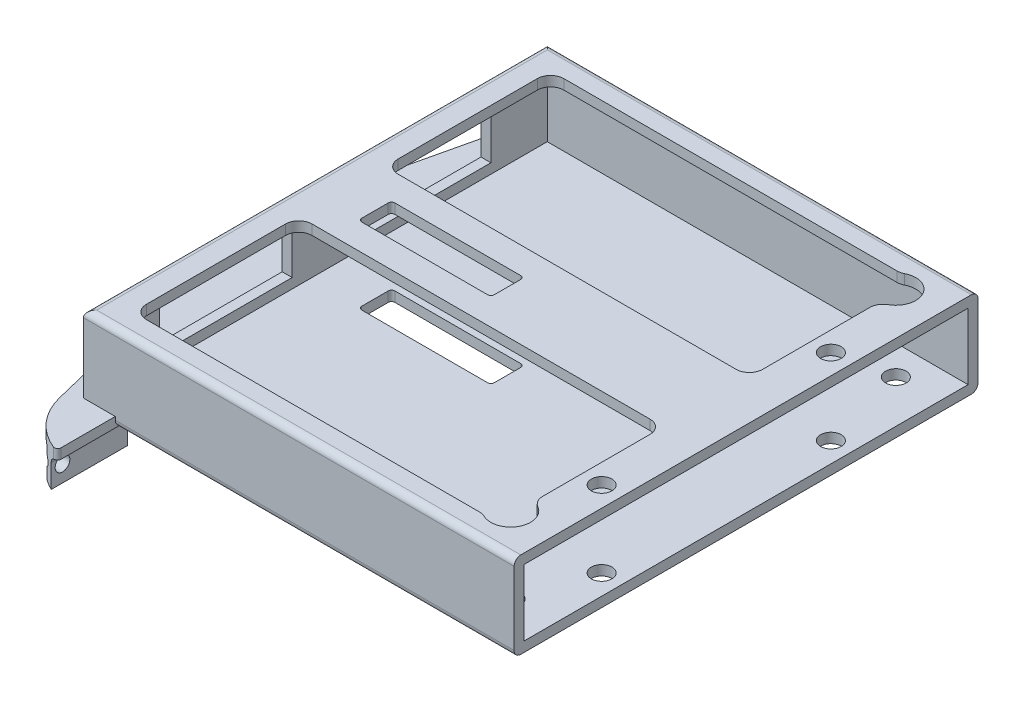
SolidWorks part; units mm, degrees
ref_plane "Front Plane" through (0, 0, 0) normal (0, 0, 1) x (1, 0, 0)
ref_plane "Top Plane" through (0, 0, 0) normal (0, 1, 0) x (1, 0, 0)
ref_plane "Right Plane" through (0, 0, 0) normal (1, 0, 0) x (0, 0, -1)
sketch "Sketch1" plane through (0, 0, 0) normal (0, 1, 0) x (1, 0, 0)
  line L0 (-33.0169, 20.6113) -> (31.9831, 20.6113)
  line L1 (-33.0169, 20.6113) -> (-33.0169, -49.3887)
  line L2 (31.9831, 20.6113) -> (31.9831, -49.3887)
  line L3 (-33.0169, -49.3887) -> (31.9831, -49.3887)
  dimension "D1" = 65
  dimension "D2" = 70
extrude "Boss-Extrude1" add sketch "Sketch1" along normal blind 13
sketch "Sketch2" plane through (31.9831, 0, 0) normal (1, 0, 0) x (0, 0, -1)
  line L0 (-49.3887, 13) -> (-49.3887, 0) construction
  line L1 (19.1113, 1.5) -> (-47.8887, 1.5)
  line L2 (19.1113, 1.5) -> (19.1113, 11.5)
  line L3 (19.1113, 11.5) -> (-47.8887, 11.5)
  line L4 (-47.8887, 1.5) -> (-47.8887, 11.5)
  line L5 (19.1113, 1.5) -> (-47.8887, 11.5) construction
  line L6 (19.1113, 11.5) -> (-47.8887, 1.5) construction
  line L7 (-49.3887, 13) -> (20.6113, 13) construction
  point P0 (-14.3887, 6.5)
  dimension "D1" = 10
  dimension "D2" = 67
  dimension "D3" = 1.5
  dimension "D4" = 1.5
extrude "Cut-Extrude1" cut sketch "Sketch2" against normal blind 63.5
sketch "Sketch3" plane through (0, 1.5, 0) normal (0, 1, 0) x (1, 0, 0)
  line L0 (-28.2071, 20.6236) -> (-28.2071, 29.1471)
  line L1 (-28.2071, 29.1471) -> (-33.524, 29.1471)
  line L2 (-33.524, 29.1471) -> (-42.092, -7.7502)
  line L3 (-42.092, -7.7502) -> (-42.092, -21.5442)
  line L4 (-42.092, -21.5442) -> (-33.1028, -58.3159)
  line L5 (-33.1028, -58.3159) -> (-28.2071, -58.3159)
  line L6 (-28.2071, -58.3159) -> (-28.2071, 20.6236)
extrude "Boss-Extrude2" add sketch "Sketch3" against normal blind 1.5
sketch "Sketch6" plane through (0, 0, 0) normal (0, -1, 0) x (1, 0, 0)
  line L0 (-31.2353, 58.3148) -> (-31.2067, 46.3148)
  line L1 (-31.2353, 58.3148) -> (-29.4971, 58.3189)
  line L2 (-31.2067, 46.3148) -> (-29.4684, 46.3189)
  line L3 (-29.4971, 58.3189) -> (-29.4684, 46.3189)
  line L4 (-41.6271, 19.1523) -> (-33.1621, 27.6578)
  line L5 (-41.6271, 19.1523) -> (-40.1511, 17.6834)
  line L6 (-33.1621, 27.6578) -> (-31.6861, 26.1889)
  line L7 (-40.1511, 17.6834) -> (-31.6861, 26.1889)
  line L8 (-41.6158, 9.7168) -> (-32.9952, 0.9548)
  line L9 (-41.6158, 9.7168) -> (-40.199, 11.1107)
  line L10 (-32.9952, 0.9548) -> (-31.5784, 2.3487)
  line L11 (-40.199, 11.1107) -> (-31.5784, 2.3487)
  line L12 (-31.1305, -17.4207) -> (-31.1305, -29.1471)
  line L13 (-31.1305, -17.4207) -> (-29.0648, -17.4207)
  line L14 (-31.1305, -29.1471) -> (-29.0648, -29.1471)
  line L15 (-29.0648, -17.4207) -> (-29.0648, -29.1471)
  line L16 (-31.1305, -17.4207) -> (-31.1305, -29.4207) construction
  line L17 (-28.2071, -29.1471) -> (-33.524, -29.1471) construction
extrude "Boss-Extrude4" add sketch "Sketch6" along normal blind 4.5
sketch "Sketch7" plane through (-33.0169, 0, 0) normal (-1, 0, 0) x (0, 0, 1)
  line L0 (-10.6113, 11.5) -> (9.3887, 11.5)
  line L1 (-10.6113, 11.5) -> (-10.6113, 3)
  line L2 (9.3887, 11.5) -> (9.3887, 3)
  line L3 (-10.6113, 3) -> (9.3887, 3)
  line L4 (19.3887, 11.5) -> (39.3887, 11.5)
  line L5 (19.3887, 11.5) -> (19.3887, 3)
  line L6 (39.3887, 11.5) -> (39.3887, 3)
  line L7 (19.3887, 3) -> (39.3887, 3)
  line L8 (-20.6113, 13) -> (49.3887, 13) construction
  line L9 (49.3887, 13) -> (49.3887, 1.5) construction
  line L10 (-20.6113, 13) -> (-20.6113, 1.5) construction
  dimension "D1" = 8.5
  dimension "D2" = 20
  dimension "D3" = 20
  dimension "D4" = 8.5
  dimension "D5" = 1.5
  dimension "D6" = 10
  dimension "D7" = 10
  dimension "D8" = 1.5
extrude "Cut-Extrude2" cut sketch "Sketch7" against normal through all
sketch "Sketch9" plane through (0, 0, 0) normal (0, -1, 0) x (1, 0, 0)
  circle A0 centre (25.5429, -14.6601) radius 1.55
  circle A1 centre (25.4661, 43.3958) radius 1.55
  dimension "D1" = 3.1
  dimension "D2" = 3.1
extrude "Cut-Extrude3" cut sketch "Sketch9" against normal blind 5.5
sketch "Sketch10" plane through (0, 13, 0) normal (0, 1, 0) x (1, 0, 0)
  line L0 (31.9831, -49.3887) -> (31.9831, 20.6113) construction
  line L1 (-29.0169, 17.1113) -> (25.9831, 17.1113)
  line L2 (-29.0169, 17.1113) -> (-29.0169, -7.8887)
  line L3 (-29.0169, -7.8887) -> (25.9831, -7.8887)
  line L4 (25.9831, 17.1113) -> (25.9831, -7.8887)
  line L5 (-29.0169, -20.8887) -> (25.9831, -20.8887)
  line L6 (-29.0169, -20.8887) -> (-29.0169, -45.8887)
  line L7 (-29.0169, -45.8887) -> (25.9831, -45.8887)
  line L8 (25.9831, -20.8887) -> (25.9831, -45.8887)
  line L9 (31.9831, 20.6113) -> (-33.0169, 20.6113) construction
  line L10 (-33.0169, -49.3887) -> (31.9831, -49.3887) construction
  dimension "D1" = 55
  dimension "D2" = 55
  dimension "D3" = 25
  dimension "D4" = 25
  dimension "D5" = 6
  dimension "D6" = 3.5
  dimension "D7" = 3.5
  dimension "D8" = 6
extrude "Cut-Extrude4" cut sketch "Sketch10" against normal blind 5.5
sketch "Sketch11" plane through (0, 13, 0) normal (0, 1, 0) x (1, 0, 0)
  circle A0 centre (25.5429, 14.6601) radius 3
  circle A1 centre (25.4661, -43.3958) radius 3
  dimension "D1" = 6
  dimension "D2" = 6
extrude "Cut-Extrude5" cut sketch "Sketch11" against normal blind 5.5
fillet "Fillet1" radius 2 4 edges at (23.7972, 12.25, 45.8887) (25.9831, 12.25, 40.4407) (25.9831, 12.25, -11.6926) (23.8133, 12.25, -17.1113)
fillet "Fillet3" radius 10 2 edges at (-42.092, 0.75, 7.7502) (-42.092, 0.75, 21.5442)
sketch "Sketch12" plane through (0, -4.5, 0) normal (0, -1, 0) x (1, 0, 0)
  line L16 (-33.1098, 58.2873) -> (-28.2071, 58.2873)
  line L17 (-33.1098, 58.2873) -> (-33.1098, 58.442)
  line L18 (-28.2071, 58.2873) -> (-28.2071, 58.442)
  line L19 (-33.1098, 58.442) -> (-28.2071, 58.442)
  line L20 (-41.8059, 22.7143) -> (-33.1028, 58.3159) construction
  line L21 (-28.2071, 58.3159) -> (-28.2071, 49.3887) construction
extrude "Cut-Extrude7" cut sketch "Sketch12" against normal through all
fillet "Fillet4" radius 10 2 edges at (-33.524, 0.75, -29.1471) (-33.1098, 0.75, 58.2873)
fillet "Fillet5" radius 1 5 edges at (1.888, 0, -20.6113) (1.888, 0, 49.3887) (-0.5169, 13, 49.3887) (-0.5169, 13, -20.6113) (-33.0169, 13, 14.3887)
fillet "Fillet6" radius 1 9 edges at (-30.0977, 0, -17.4207) (-40.9074, 0, 10.4137) (-35.8887, 0, 6.7297) (-32.2868, 0, 1.6517) (-32.4241, 0, 26.9234) (-35.9186, 0, 21.9361) (-40.8891, 0, 18.4179) (-30.3375, 0, 46.3169) (-29.4821, 0, 52.045)
fillet "Fillet7" radius 0.5 1 edges at (-29.0648, 0, -22.6418)
fillet "Fillet8" radius 0.5 2 edges at (-28.2071, 0.75, 58.2873) (-28.2071, 0.75, -29.1471)
sketch "Sketch13" plane through (0, 13, 0) normal (0, 1, 0) x (1, 0, 0)
  circle A0 centre (28.943, 1.4519) radius 1.55
  circle A1 centre (28.943, -33.1424) radius 1.55
  dimension "D1" = 3.1
  dimension "D2" = 3.1
extrude "Cut-Extrude8" cut sketch "Sketch13" against normal through all
sketch "Sketch14" plane through (-31.0958, 0, -0.0743) normal (-1, 0, -0.0024) x (-0.0024, 0, 1)
  circle A0 centre (56.1387, -1.95) radius 1.106
extrude "Cut-Extrude9" cut sketch "Sketch14" against normal through all
sketch "Sketch15" plane through (-30.489, 0, 30.3437) normal (-0.7088, 0, 0.7054) x (0.7054, 0, 0.7088)
  circle A0 centre (-5.6953, -1.95) radius 1.15
  dimension "D1" = 2.3
extrude "Cut-Extrude10" cut sketch "Sketch15" against normal through all
sketch "Sketch16" plane through (-16.2887, 0, -16.0258) normal (-0.7128, 0, -0.7013) x (-0.7013, 0, 0.7128)
  circle A0 centre (33.1742, -1.95) radius 1.1
  dimension "D1" = 2.2
extrude "Cut-Extrude11" cut sketch "Sketch16" against normal through all
sketch "Sketch17" plane through (-31.1305, 0, 0) normal (-1, 0, 0) x (0, 0, 1)
  circle A0 centre (-19.7775, -1.95) radius 1.1
  dimension "D1" = 2.2
extrude "Cut-Extrude12" cut sketch "Sketch17" against normal through all
sketch "Sketch18" plane through (0, 13, 0) normal (0, 1, 0) x (1, 0, 0)
  line L0 (-24.0169, -11.8887) -> (-4.0169, -11.8887)
  line L1 (-24.0169, -11.8887) -> (-24.0169, -16.8887)
  line L2 (-4.0169, -11.8887) -> (-4.0169, -16.8887)
  line L3 (-24.0169, -16.8887) -> (-4.0169, -16.8887)
  line L4 (-32.0169, -14.3887) -> (31.9831, -14.3887) construction
  line L5 (-32.0169, 19.6113) -> (-32.0169, -48.3887) construction
  line L6 (31.9831, -48.3887) -> (31.9831, 19.6113) construction
  dimension "D1" = 5
  dimension "D2" = 20
  dimension "D3" = 2.5
  dimension "D4" = 8
extrude "Cut-Extrude13" cut sketch "Sketch18" against normal through all
fillet "Fillet9" radius 0.5 8 edges at (-24.0169, 0.75, 16.8887) (-24.0169, 0.75, 11.8887) (-4.0169, 0.75, 11.8887) (-4.0169, 0.75, 16.8887) (-4.0169, 12.25, 16.8887) (-4.0169, 12.25, 11.8887) (-24.0169, 12.25, 16.8887) (-24.0169, 12.25, 11.8887)
fillet "Fillet10" radius 2 6 edges at (-29.0169, 12.25, -17.1113) (-29.0169, 12.25, 7.8887) (25.9831, 12.25, 7.8887) (25.9831, 12.25, 20.8887) (-29.0169, 12.25, 45.8887) (-29.0169, 12.25, 20.8887)
